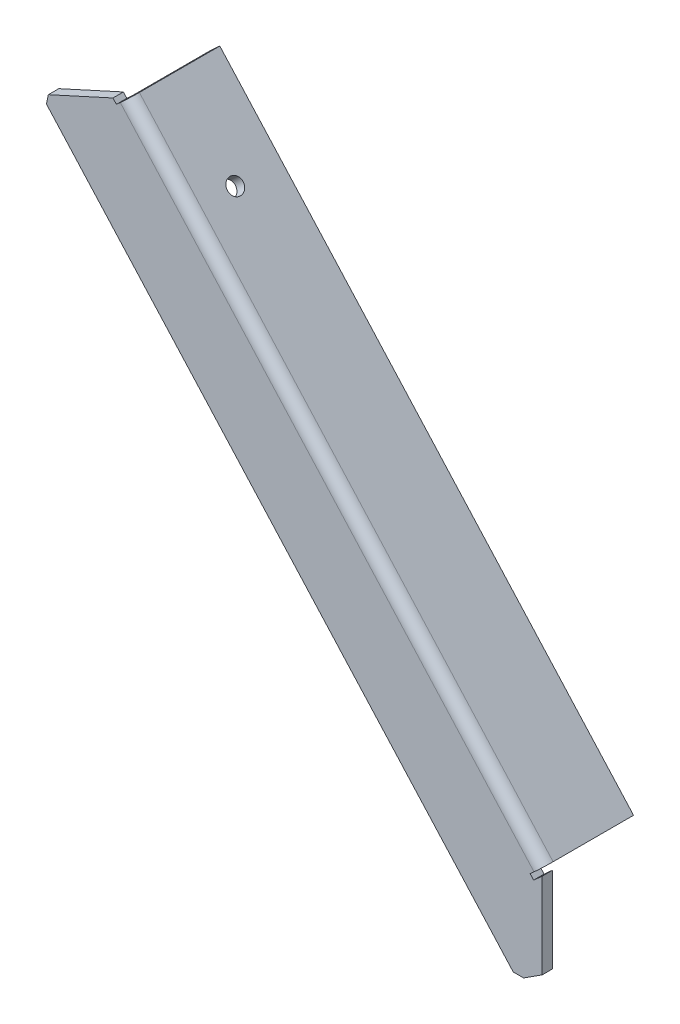
SolidWorks part; units mm, degrees
note: The reader was unsure of these and kept them because the rebuilt part matched: flange length of "Edge-Flange1".
material "ASTM A36 Steel"
ref_plane "Front Plane" through (0, 0, 0) normal (0, 0, 1) x (1, 0, 0)
ref_plane "Top Plane" through (0, 0, 0) normal (0, 1, 0) x (1, 0, 0)
ref_plane "Right Plane" through (0, 0, 0) normal (1, 0, 0) x (0, 0, -1)
sketch "Sketch1" plane through (0, 0, 0) normal (0, 0, 1) x (1, 0, 0)
  line L0 (0, 22.5) -> (-158.4558, 198.4261)
  line L1 (-11.0762, -17.5) -> (-189.844, 180.9776)
  line L2 (-11.0762, -17.5) -> (-7.0762, -17.5)
  line L4 (-26.0063, -0.9238) -> (-184.4621, 175.0024) construction
  line L6 (0, 22.5) -> (0, -12.9354)
  line L8 (0, -12.9354) -> (-7.0762, -17.5)
  line L9 (-158.4558, 198.4261) -> (-189.1219, 184.4508)
  line L11 (-189.844, 180.9776) -> (-189.1219, 184.4508)
  dimension "D2" = 4
  dimension "D1" = 35
base flange "Base-Flange1" sketch "Sketch1" thickness 4 reverse thickness direction no parameters "D1"=0.2
edge flange "Edge-Flange1" sketch "Sketch8" flange angle 90 flange length 35 flange position material inside bend radius 0.2 thickness 4 relief rectangular parameters "D6"=10
sketch "Sketch8" plane through (11.1887, 10.0777, -4) normal (-0.743, -0.6693, 0) x (-0.6693, 0.743, 0)
  line L2 (16.7183, 0) -> (16.7183, 31)
  line L3 (16.7183, 31) -> (253.4846, 31)
  line L4 (253.4846, 31) -> (253.4846, 0)
  line L5 (253.4846, 0) -> (16.7183, 0) construction
  line L6 (253.4846, 0) -> (16.7183, 0)
bend "EdgeBend1" bend radius 0.2 bend angle 90 parameters "D5"=1
sketch "Sketch9" plane through (11.1887, 10.0777, 0) normal (0.743, 0.6693, 0) x (0, 0, -1)
  line L0 (4.2, 253.4846) -> (35, 253.4846) construction
  line L1 (35, 253.4846) -> (35, 16.7183) construction
  circle A0 centre (17.5, 218.4846) radius 3
  dimension "D1" = 6
  dimension "D2" = 35
  dimension "D3" = 17.5
extrude "Cut-Extrude1" cut sketch "Sketch9" against normal blind 10 normal cut yes
sketch "Bend-Lines1" [suppressed] plane through (0, 0, 0) normal (0, 1, 0) x (1, 0, 0)
sketch "Bounding-Box1" [suppressed] plane through (0, 0, 0) normal (0, 1, 0) x (1, 0, 0)
sheet metal parameters "Sheet-Metal1" thickness 4 parameters "D1"=0.2
flat pattern "Flat-Pattern1" [suppressed]
sketch "Bend-Lines2" plane through (0, 0, 0) normal (0, 1, 0) x (1, 0, 0)
sketch3d "Bounding-Box2" [suppressed]
  line L0 (165.2414, 205.9598, 0) -> (-17.6213, 2.9359, 0) construction
  line L1 (191.2477, 182.5361, 0) -> (8.385, -20.4878, 0) construction
  line L2 (165.2414, 205.9598, 0) -> (191.2477, 182.5361, 0) construction
  line L3 (-17.6213, 2.9359, 0) -> (8.385, -20.4878, 0) construction
sheet metal parameters "Sheet-Metal2" thickness 4 parameters "D1"=0.2
flat pattern "Flat-Pattern1"
sketch "Bend-Lines2" plane through (0, 0, 0) normal (0, 0, 1) x (1, 0, 0)
  line L0 (-1.8369, 20.8455) -> (-160.2927, 196.7717) construction
  line L1 (-1.8369, 20.8455) -> (-160.2927, 196.7717) construction
sketch3d "Bounding-Box2" [suppressed]
  line L0 (-142.9088, 226.0747, 0) -> (39.9538, 23.0508, 0) construction
  line L1 (-191.2477, 182.5361, 0) -> (-8.385, -20.4878, 0) construction
  line L2 (-142.9088, 226.0747, 0) -> (-191.2477, 182.5361, 0) construction
  line L3 (39.9538, 23.0508, 0) -> (-8.385, -20.4878, 0) construction
bend of the flat pattern "Flatten-<EdgeBend1>1"
sheet metal parameters "Sheet-Metal3" thickness 4 parameters "D1"=0.2
flat pattern "Flat-Pattern1"
sketch "Bend-Lines2" plane through (0, 0, 0) normal (0, 0, 1) x (1, 0, 0)
  line L0 (-1.8369, 20.8455) -> (-160.2927, 196.7717) construction
  line L1 (-1.8369, 20.8455) -> (-160.2927, 196.7717) construction
sketch3d "Bounding-Box2" [suppressed]
  line L0 (-142.9088, 226.0747, 0) -> (39.9538, 23.0508, 0) construction
  line L1 (-191.2477, 182.5361, 0) -> (-8.385, -20.4878, 0) construction
  line L2 (-142.9088, 226.0747, 0) -> (-191.2477, 182.5361, 0) construction
  line L3 (39.9538, 23.0508, 0) -> (-8.385, -20.4878, 0) construction
bend of the flat pattern "Flatten-<EdgeBend1>1"
